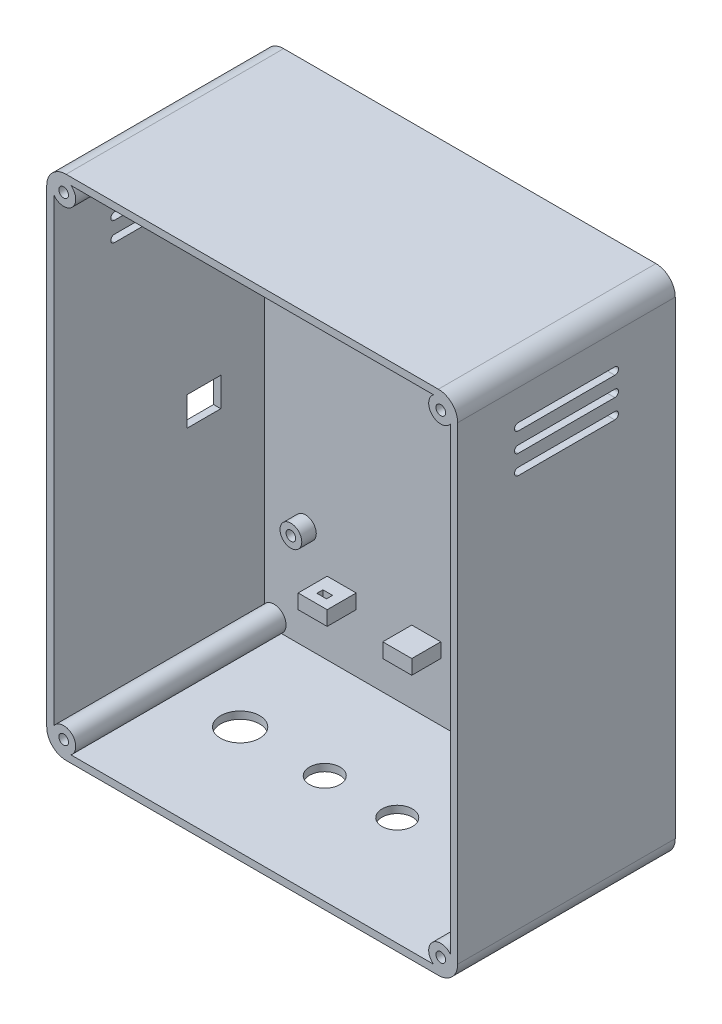
SolidWorks part; units mm, degrees
ref_plane "Front Plane" through (0, 0, 0) normal (0, 0, 1) x (1, 0, 0)
ref_plane "Top Plane" through (0, 0, 0) normal (0, 1, 0) x (1, 0, 0)
ref_plane "Right Plane" through (0, 0, 0) normal (1, 0, 0) x (0, 0, -1)
sketch "Sketch1" plane through (0, 0, 0) normal (0, 0, 1) x (1, 0, 0)
  line L0 (-77, 0) -> (77, 0)
  line L1 (85, 8) -> (85, 202)
  line L2 (77, 210) -> (-77, 210)
  line L3 (-85, 202) -> (-85, 8)
  arc A0 (-85, 8) -> (-77, 0) centre (-77, 8) ccw
  arc A1 (77, 0) -> (85, 8) centre (77, 8) ccw
  arc A2 (85, 202) -> (77, 210) centre (77, 202) ccw
  arc A3 (-77, 210) -> (-85, 202) centre (-77, 202) ccw
extrude "Block" add sketch "Sketch1" along normal blind 90
shell "Shell1" thickness 3 removed face at (0, 105, 90)
sketch "Sketch2" plane through (0, 0, 0) normal (0, 0, 1) x (1, 0, 0)
  circle A0 centre (-78, 7) radius 5
  circle A1 centre (78, 7) radius 5
  circle A2 centre (-78, 203) radius 5
  circle A3 centre (78, 203) radius 5
extrude "Corner columns" add sketch "Sketch2" along normal blind 90
ref_plane "P1_Front_90" through (0, 0, 90) normal (0, 0, 1) x (1, 0, 0)
sketch "Sketch3" plane through (0, 0, 90) normal (0, 0, 1) x (1, 0, 0)
  circle A0 centre (-78, 7) radius 2
  circle A1 centre (78, 7) radius 2
  circle A2 centre (-78, 203) radius 2
  circle A3 centre (78, 203) radius 2
extrude "Front panel insert holes" cut sketch "Sketch3" against normal blind 7
ref_plane "P2_Front_3" through (0, 0, 3) normal (0, 0, 1) x (1, 0, 0)
sketch "Sketch4" plane through (0, 0, 3) normal (0, 0, 1) x (1, 0, 0)
  circle A0 centre (-65, 46) radius 4.5
  circle A1 centre (65, 46) radius 4.5
  circle A2 centre (-65, 190) radius 4.5
  circle A3 centre (65, 190) radius 4.5
extrude "Plate bosses" add sketch "Sketch4" along normal blind 6
ref_plane "P3_Front_9" through (0, 0, 9) normal (0, 0, 1) x (1, 0, 0)
sketch "Sketch5" plane through (0, 0, 9) normal (0, 0, 1) x (1, 0, 0)
  circle A0 centre (-65, 46) radius 2
  circle A1 centre (65, 46) radius 2
  circle A2 centre (-65, 190) radius 2
  circle A3 centre (65, 190) radius 2
extrude "Plate insert holes" cut sketch "Sketch5" against normal blind 7
sketch "Sketch6" plane through (0, 0, 0) normal (0, 1, 0) x (1, 0, 0)
  circle A0 centre (-50, -45) radius 8.1
  circle A1 centre (-15, -45) radius 6.3
  circle A2 centre (15, -45) radius 6.3
  circle A3 centre (50, -45) radius 6.3
extrude "Cable gland holes" cut sketch "Sketch6" along normal blind 4
sketch "Sketch7" plane through (0, 0, 3) normal (0, 0, 1) x (1, 0, 0)
  line L1 (-56, 27) -> (-44, 27)
  line L2 (-56, 27) -> (-56, 33)
  line L3 (-56, 33) -> (-44, 33)
  line L4 (-44, 27) -> (-44, 33)
  line L5 (-56, 27) -> (-44, 33) construction
  line L6 (-56, 33) -> (-44, 27) construction
  line L7 (-21, 27) -> (-9, 27)
  line L8 (-21, 27) -> (-21, 33)
  line L9 (-21, 33) -> (-9, 33)
  line L10 (-9, 27) -> (-9, 33)
  line L11 (-21, 27) -> (-9, 33) construction
  line L12 (-21, 33) -> (-9, 27) construction
  line L13 (9, 27) -> (21, 27)
  line L14 (9, 27) -> (9, 33)
  line L15 (9, 33) -> (21, 33)
  line L16 (21, 27) -> (21, 33)
  line L17 (9, 27) -> (21, 33) construction
  line L18 (9, 33) -> (21, 27) construction
  line L19 (44, 27) -> (56, 27)
  line L20 (44, 27) -> (44, 33)
  line L21 (44, 33) -> (56, 33)
  line L22 (56, 27) -> (56, 33)
  line L23 (44, 27) -> (56, 33) construction
  line L24 (44, 33) -> (56, 27) construction
  point P0 (-15, 30)
  point P9 (15, 30)
  point P14 (50, 30)
extrude "Cable tie bars" add sketch "Sketch7" along normal blind 12
ref_plane "P4_Top_26.99" through (0, 26.99, 0) normal (0, 1, 0) x (1, 0, 0)
sketch "Sketch8" plane through (0, 26.99, 0) normal (0, 1, 0) x (1, 0, 0)
  line L1 (-52, -11.25) -> (-48, -11.25)
  line L2 (-52, -11.25) -> (-52, -8.75)
  line L3 (-52, -8.75) -> (-48, -8.75)
  line L4 (-48, -11.25) -> (-48, -8.75)
  line L5 (-52, -11.25) -> (-48, -8.75) construction
  line L6 (-52, -8.75) -> (-48, -11.25) construction
  line L7 (13, -13.75) -> (17, -13.75)
  line L8 (13, -13.75) -> (13, -8.75)
  line L9 (13, -8.75) -> (17, -8.75)
  line L10 (17, -13.75) -> (17, -8.75)
  line L11 (13, -13.75) -> (17, -8.75) construction
  line L12 (13, -8.75) -> (17, -13.75) construction
  line L13 (48, -13.75) -> (52, -13.75)
  line L14 (48, -13.75) -> (48, -8.75)
  line L15 (48, -8.75) -> (52, -8.75)
  line L16 (52, -13.75) -> (52, -8.75)
  line L17 (48, -13.75) -> (52, -8.75) construction
  line L18 (48, -8.75) -> (52, -13.75) construction
  point P0 (15, -11.25)
  point P9 (50, -11.25)
extrude "Cable tie slots" cut sketch "Sketch8" along normal blind 6.02
ref_plane "P5_Right_-85" through (-85, 0, 0) normal (1, 0, 0) x (0, 0, -1)
sketch "Sketch9" plane through (-85, 0, 0) normal (1, 0, 0) x (0, 0, -1)
  line L1 (-35, 89) -> (-21, 89)
  line L2 (-35, 89) -> (-35, 101)
  line L3 (-35, 101) -> (-21, 101)
  line L4 (-21, 89) -> (-21, 101)
  line L5 (-35, 89) -> (-21, 101) construction
  line L6 (-35, 101) -> (-21, 89) construction
extrude "USB access" cut sketch "Sketch9" along normal blind 4
ref_plane "P6_Right_-85" through (-85, 0, 0) normal (1, 0, 0) x (0, 0, -1)
sketch "Sketch10" plane through (-85, 0, 0) normal (1, 0, 0) x (0, 0, -1)
  line L0 (-25, 172) -> (-65, 172) construction
  line L1 (-25, 170.5) -> (-65, 170.5)
  line L2 (-25, 173.5) -> (-65, 173.5)
  line L3 (-25, 180) -> (-65, 180) construction
  line L4 (-25, 178.5) -> (-65, 178.5)
  line L5 (-25, 181.5) -> (-65, 181.5)
  line L6 (-25, 188) -> (-65, 188) construction
  line L7 (-25, 186.5) -> (-65, 186.5)
  line L8 (-25, 189.5) -> (-65, 189.5)
  arc A0 (-25, 170.5) -> (-25, 173.5) centre (-25, 172) ccw
  arc A1 (-65, 173.5) -> (-65, 170.5) centre (-65, 172) ccw
  arc A2 (-25, 178.5) -> (-25, 181.5) centre (-25, 180) ccw
  arc A3 (-65, 181.5) -> (-65, 178.5) centre (-65, 180) ccw
  arc A4 (-25, 186.5) -> (-25, 189.5) centre (-25, 188) ccw
  arc A5 (-65, 189.5) -> (-65, 186.5) centre (-65, 188) ccw
  point P2 (-45, 172)
  point P7 (-45, 180)
  point P14 (-45, 188)
  point P21 (0, 0)
extrude "Vents left" cut sketch "Sketch10" along normal blind 4
ref_plane "P7_Right_85" through (85, 0, 0) normal (1, 0, 0) x (0, 0, -1)
sketch "Sketch11" plane through (85, 0, 0) normal (1, 0, 0) x (0, 0, -1)
  line L0 (-25, 172) -> (-65, 172) construction
  line L1 (-25, 170.5) -> (-65, 170.5)
  line L2 (-25, 173.5) -> (-65, 173.5)
  line L3 (-25, 180) -> (-65, 180) construction
  line L4 (-25, 178.5) -> (-65, 178.5)
  line L5 (-25, 181.5) -> (-65, 181.5)
  line L6 (-25, 188) -> (-65, 188) construction
  line L7 (-25, 186.5) -> (-65, 186.5)
  line L8 (-25, 189.5) -> (-65, 189.5)
  arc A0 (-25, 170.5) -> (-25, 173.5) centre (-25, 172) ccw
  arc A1 (-65, 173.5) -> (-65, 170.5) centre (-65, 172) ccw
  arc A2 (-25, 178.5) -> (-25, 181.5) centre (-25, 180) ccw
  arc A3 (-65, 181.5) -> (-65, 178.5) centre (-65, 180) ccw
  arc A4 (-25, 186.5) -> (-25, 189.5) centre (-25, 188) ccw
  arc A5 (-65, 189.5) -> (-65, 186.5) centre (-65, 188) ccw
  point P2 (-45, 172)
  point P7 (-45, 180)
  point P14 (-45, 188)
  point P21 (0, 0)
extrude "Vents right" cut sketch "Sketch11" against normal blind 4
sketch "Sketch12" plane through (0, 0, 0) normal (0, 0, 1) x (1, 0, 0)
  circle A0 centre (-45, 165) radius 4.75
  circle A1 centre (45, 165) radius 4.75
extrude "Keyhole heads" cut sketch "Sketch12" along normal blind 4
sketch "Sketch13" plane through (0, 0, 0) normal (0, 0, 1) x (1, 0, 0)
  line L0 (-45, 165) -> (-45, 176) construction
  line L1 (-47.4, 165) -> (-47.4, 176)
  line L2 (-42.6, 165) -> (-42.6, 176)
  line L3 (45, 165) -> (45, 176) construction
  line L4 (42.6, 165) -> (42.6, 176)
  line L5 (47.4, 165) -> (47.4, 176)
  arc A0 (-47.4, 165) -> (-42.6, 165) centre (-45, 165) ccw
  arc A1 (-42.6, 176) -> (-47.4, 176) centre (-45, 176) ccw
  arc A2 (42.6, 165) -> (47.4, 165) centre (45, 165) ccw
  arc A3 (47.4, 176) -> (42.6, 176) centre (45, 176) ccw
  point P2 (-45, 170.5)
  point P7 (45, 170.5)
  point P14 (0, 0)
extrude "Keyhole slots" cut sketch "Sketch13" along normal blind 4
